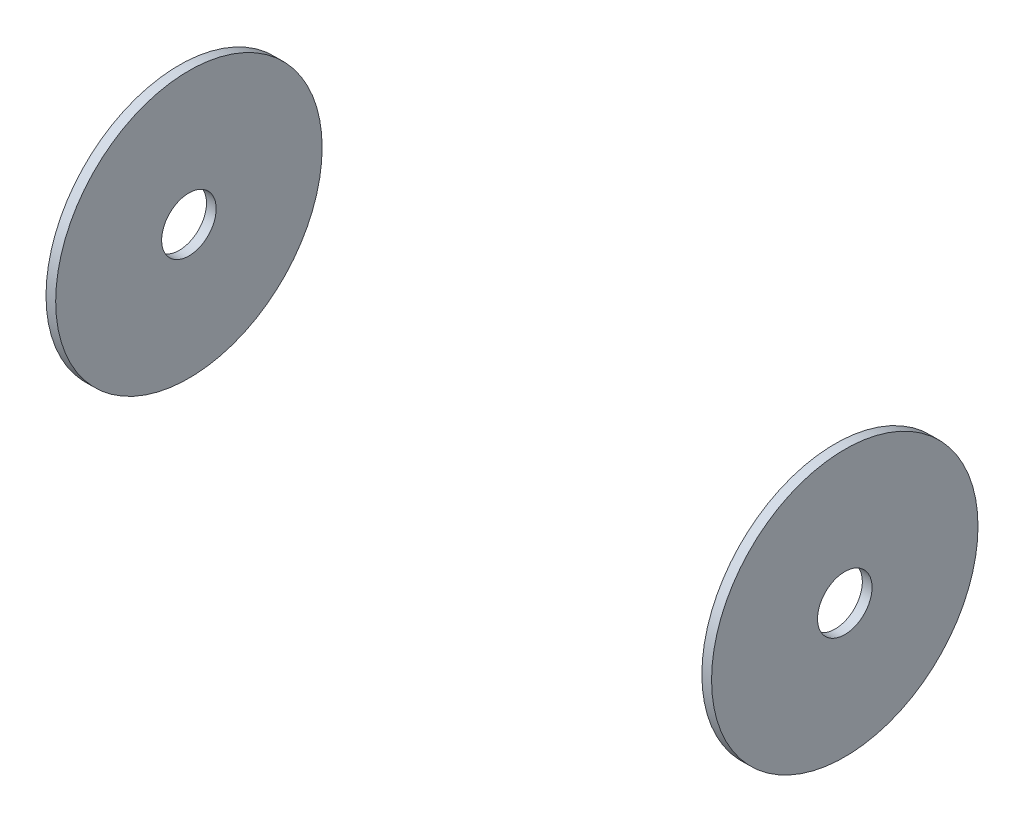
SolidWorks part; units mm, degrees
material "Titanium"
ref_plane "Front Plane" through (0, 0, 0) normal (0, 0, 1) x (1, 0, 0)
ref_plane "Top Plane" through (0, 0, 0) normal (0, 1, 0) x (1, 0, 0)
ref_plane "Right Plane" through (0, 0, 0) normal (1, 0, 0) x (0, 0, -1)
sketch "Sketch1" plane through (50.05, 0, 0) normal (1, 0, 0) x (0, 0, -1)
  circle A0 centre (-177.8, 26.9875) radius 20.6375
  arc A1 (-196.4827, 35.7546) -> (-198.1234, 23.4009) centre (-177.8, 26.9875) ccw construction
  circle A2 centre (-177.8, 26.9875) radius 4.2227
  dimension "D1" = 8.4455
extrude "Boss-Extrude1" add sketch "Sketch1" along normal blind 1.5
mirror "Mirror2" about plane through (0, 0, 0) normal (1, 0, 0) of bodies 101
equation "\"weapon shaft threads\"= 5 / 16"
equation "\"D1@Sketch1\"=\"weapon shaft threads\" + .02in"
equation "\"D1@Boss-Extrude1\"=1.5mm"
